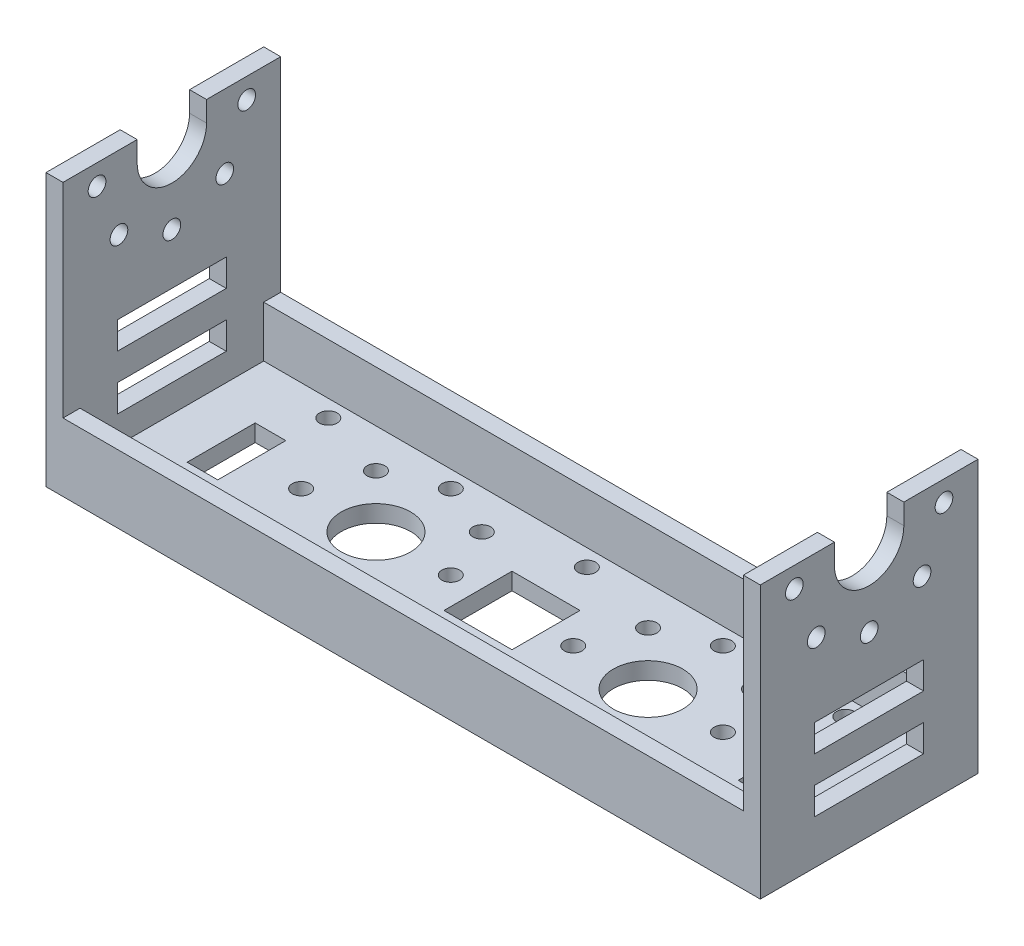
SolidWorks part; units mm, degrees
material "7075-T6 (SN)"
ref_plane "Front Plane" through (0, 0, 0) normal (0, 0, 1) x (1, 0, 0)
ref_plane "Top Plane" through (0, 0, 0) normal (0, 1, 0) x (1, 0, 0)
ref_plane "Right Plane" through (0, 0, 0) normal (1, 0, 0) x (0, 0, -1)
sketch "Sketch2" plane through (0, 0, 0) normal (0, 1, 0) x (1, 0, 0)
  line L0 (0, 0) -> (0, 657.6637) construction
  line L1 (0, 0) -> (1206.8272, 0) construction
  line L3 (-52.5, 16) -> (52.5, 16)
  line L4 (-52.5, 16) -> (-52.5, -16)
  line L5 (-52.5, -16) -> (52.5, -16)
  line L6 (52.5, 16) -> (52.5, -16)
  dimension "D1" = 32
  dimension "D2" = 105
extrude "Boss-Extrude1" add sketch "Sketch2" along normal blind 40
sketch "Sketch3" plane through (0, 40, 0) normal (0, 1, 0) x (1, 0, 0)
  line L0 (52.5, 16) -> (-52.5, 16) construction
  line L1 (-50, 16) -> (50, 16)
  line L2 (-50, 16) -> (-50, -16)
  line L3 (-50, -16) -> (50, -16)
  line L4 (50, 16) -> (50, -16)
  line L5 (-52.5, -16) -> (52.5, -16) construction
  line L6 (-52.5, 16) -> (-52.5, -16) construction
  line L7 (52.5, -16) -> (52.5, 16) construction
  dimension "D1" = 2.5
  dimension "D2" = 2.5
extrude "Cut-Extrude1" cut sketch "Sketch3" against normal blind 30
sketch "Sketch4" plane through (0, 10, 0) normal (0, 1, 0) x (1, 0, 0)
  line L0 (-50, 16) -> (-50, -16) construction
  line L1 (-50, 13.5) -> (50, 13.5)
  line L2 (-50, 13.5) -> (-50, -13.5)
  line L3 (-50, -13.5) -> (50, -13.5)
  line L4 (50, 13.5) -> (50, -13.5)
  line L5 (50, -16) -> (50, 16) construction
  line L6 (50, 16) -> (-50, 16) construction
  line L7 (-50, -16) -> (50, -16) construction
  dimension "D1" = 2.5
  dimension "D2" = 2.5
extrude "Cut-Extrude2" cut sketch "Sketch4" against normal blind 7.5
sketch "Sketch5" plane through (0, 0, 0) normal (0, -1, 0) x (1, 0, 0)
  line L0 (0, 0) -> (71.5175, 0) construction
  line L1 (0, 0) -> (0, 30.8433) construction
  line L2 (50, 13.5) -> (50, -13.5) construction
  point P3 (20, 0)
  point P7 (20, -11)
  point P8 (-20, 0)
  point P9 (38, 11)
  point P11 (38, -11)
  dimension "D1" = 30
  dimension "D2" = 11
  dimension "D3" = 11
  dimension "D4" = 76
hole_wizard "Ø10.0mm Dowel Hole1" positions "Sketch8" profile "Sketch9" hole size "Ø10.0" standard "ISO" end condition through all
sketch "Sketch8" plane through (0, 0, 0) normal (0, -1, 0) x (-1, 0, 0)
  point P0 (-20, 0)
  point P3 (20, 0)
sketch "Sketch9" plane through (20, 0, 0) normal (1, 0, 0) x (0, 0, -1)
  line L0 (0, 0) -> (0, 40)
  line L1 (0, 40) -> (5.1, 40)
  line L2 (5.1, 40) -> (5.1, 0)
  line L5 (5.1, 0) -> (0, 0)
  line L11 (0, -6.35) -> (0, 107.95) construction
  dimension "Thru Hole Dia." = 10.2
  dimension "Thru Hole Depth" = 40
hole_wizard "Ø2.5mm Dowel Hole1" positions "Sketch10" profile "Sketch11" hole size "Ø2.5" standard "ISO" end condition through all
sketch "Sketch10" plane through (0, 0, 0) normal (0, -1, 0) x (-1, 0, 0)
  point P0 (-20, 11)
sketch "Sketch11" plane through (20, 0, -11) normal (1, 0, 0) x (0, 0, -1)
  line L0 (0, 0) -> (0, 40)
  line L1 (0, 40) -> (1.3, 40)
  line L2 (1.3, 40) -> (1.3, 0)
  line L5 (1.3, 0) -> (0, 0)
  line L11 (0, -6.35) -> (0, 107.95) construction
  dimension "Thru Hole Dia." = 2.6
  dimension "Thru Hole Depth" = 40
pattern_circular "CirPattern1" count 8 over 360 about axis through (20, 0, 0) along (0, -1, 0) of "Ø2.5mm Dowel Hole1"
hole_wizard "Ø2.5mm Dowel Hole2" positions "Sketch12" profile "Sketch13" hole size "Ø2.5" standard "ISO" end condition through all
sketch "Sketch12" plane through (0, 0, 0) normal (0, -1, 0) x (-1, 0, 0)
  point P0 (-38, 11)
  point P3 (-38, -11)
sketch "Sketch13" plane through (38, 0, -11) normal (1, 0, 0) x (0, 0, -1)
  line L0 (0, 0) -> (0, 40)
  line L1 (0, 40) -> (1.3, 40)
  line L2 (1.3, 40) -> (1.3, 0)
  line L5 (1.3, 0) -> (0, 0)
  line L11 (0, -6.35) -> (0, 107.95) construction
  dimension "Thru Hole Dia." = 2.6
  dimension "Thru Hole Depth" = 40
pattern_linear "LPattern1" count 3 spacing 38 along (-1, 0, 0) of "Ø2.5mm Dowel Hole2"
mirror "Mirror1" about plane through (0, 0, 0) normal (1, 0, 0) of "CirPattern1"
sketch "Sketch14" plane through (0, 0, 0) normal (1, 0, 0) x (0, 0, -1)
  line L0 (0, 0) -> (0, 54.5785) construction
  line L1 (-16, 40) -> (16, 40) construction
  line L2 (-5.1, 40) -> (5.1, 40)
  line L3 (-5.1, 40) -> (-5.1, 37)
  line L5 (5.1, 40) -> (5.1, 37)
  arc A0 (-5.1, 37) -> (5.1, 37) centre (0, 37) ccw
  dimension "D1" = 5.1
  dimension "D2" = 3
extrude "Cut-Extrude3" cut sketch "Sketch14" against normal mid plane 145.5
sketch "Sketch15" plane through (52.5, 0, 0) normal (1, 0, 0) x (0, 0, -1)
  arc A0 (-5.1, 37) -> (5.1, 37) centre (0, 37) ccw construction
  point P0 (11, 37)
  point P5 (0, 37)
  dimension "D1" = 11
hole_wizard "Ø2.5mm Dowel Hole3" positions "Sketch16" profile "Sketch17" hole size "Ø2.5" standard "ISO" end condition through all
sketch "Sketch16" plane through (52.5, 0, 0) normal (1, 0, 0) x (0, 0, -1)
  point P0 (11, 37)
sketch "Sketch17" plane through (52.5, 37, -11) normal (0, 1, 0) x (0, 0, -1)
  line L0 (0, 0) -> (0, 105)
  line L1 (0, 105) -> (1.3, 105)
  line L2 (1.3, 105) -> (1.3, 0)
  line L5 (1.3, 0) -> (0, 0)
  line L11 (0, -6.35) -> (0, 107.95) construction
  dimension "Thru Hole Dia." = 2.6
  dimension "Thru Hole Depth" = 105
pattern_circular "CirPattern3" count 5 every 45 about axis through (-72.75, 37, 0) along (1, 0, 0) of "Ø2.5mm Dowel Hole3" reverse direction yes
sketch "Sketch18" plane through (0, 0, 0) normal (1, 0, 0) x (0, 0, -1)
  line L0 (0, 0) -> (0, 51.1234) construction
  line L2 (-8, 14.5) -> (8, 14.5)
  line L3 (-8, 14.5) -> (-8, 18.5)
  line L4 (-8, 18.5) -> (8, 18.5)
  line L5 (8, 14.5) -> (8, 18.5)
  line L6 (-8, 14.5) -> (8, 18.5) construction
  line L7 (-8, 18.5) -> (8, 14.5) construction
  line L8 (-8, 6.5) -> (8, 6.5)
  line L9 (-8, 6.5) -> (-8, 10.5)
  line L10 (-8, 10.5) -> (8, 10.5)
  line L11 (8, 6.5) -> (8, 10.5)
  line L12 (-8, 6.5) -> (8, 10.5) construction
  line L13 (-8, 10.5) -> (8, 6.5) construction
  point P3 (0, 16.5)
  point P8 (0, 8.5)
  dimension "D1" = 16
  dimension "D2" = 4
  dimension "D3" = 18.5
  dimension "D4" = 26.5
  dimension "D5" = 4
extrude "Cut-Extrude4" cut sketch "Sketch18" against normal mid plane 145.5
sketch "Sketch19" plane through (0, 0, 0) normal (0, -1, 0) x (1, 0, 0)
  line L0 (0, 0) -> (55.3186, 0) construction
  line L1 (-5, -5) -> (5, -5)
  line L2 (-5, -5) -> (-5, 5)
  line L3 (-5, 5) -> (5, 5)
  line L4 (5, -5) -> (5, 5)
  line L5 (-5, -5) -> (5, 5) construction
  line L6 (-5, 5) -> (5, -5) construction
  line L7 (0, 0) -> (71.5175, 0) construction
  line L8 (0, 0) -> (0, 30.8433) construction
  line L9 (38.25, 5) -> (42.75, 5)
  line L10 (38.25, 5) -> (38.25, -5)
  line L11 (38.25, -5) -> (42.75, -5)
  line L12 (42.75, 5) -> (42.75, -5)
  line L13 (38.25, 5) -> (42.75, -5) construction
  line L14 (38.25, -5) -> (42.75, 5) construction
  line L15 (-38.25, -5) -> (-42.75, 5) construction
  line L16 (-38.25, 5) -> (-42.75, -5) construction
  line L17 (-42.75, 5) -> (-42.75, -5)
  line L18 (-38.25, -5) -> (-42.75, -5)
  line L19 (-38.25, 5) -> (-38.25, -5)
  line L20 (-38.25, 5) -> (-42.75, 5)
  point P0 (0, 0)
  point P10 (40.5, 0)
  point P21 (-40.5, 0)
  dimension "D1" = 10
  dimension "D2" = 10
  dimension "D3" = 4.5
  dimension "D4" = 40.5
extrude "Cut-Extrude5" cut sketch "Sketch19" against normal blind 145.5
ref_plane "Plane1" through (-20.01, 0, 0) normal (1, 0, 0) x (0, 0, -1)
ref_axis "Axis1" through (-52.5, 37, 0) along (1, 0, 0)
ref_point "Point1"
ref_axis "yaw_axis" through (-20, 44.1367, 0) along (0, -1, 0)
